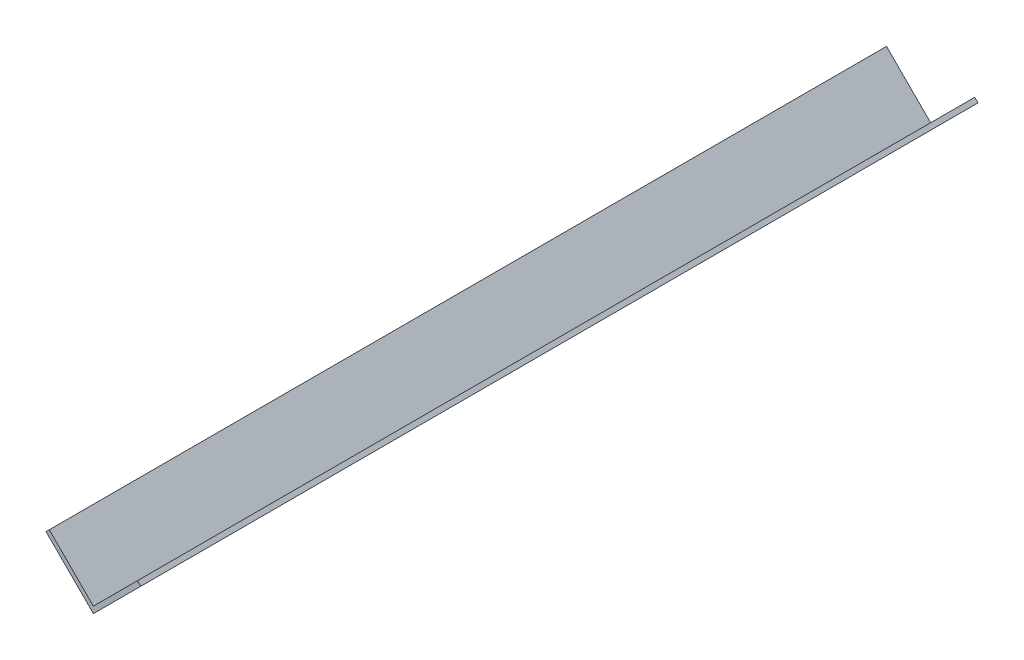
SolidWorks part; units mm, degrees
material "6061 Alloy"
ref_plane "Front Plane" through (0, 0, 0) normal (0, 0, 1) x (1, 0, 0)
ref_plane "Top Plane" through (0, 0, 0) normal (0, 1, 0) x (1, 0, 0)
ref_plane "Right Plane" through (0, 0, 0) normal (1, 0, 0) x (0, 0, -1)
sketch "Sketch1" plane through (0, 0, 0) normal (0, 0, 1) x (1, 0, 0)
  line L0 (0, 0) -> (-17.9605, 17.9605)
  line L1 (-17.9605, 17.9605) -> (-16.7257, 19.1953)
  line L2 (-16.7257, 19.1953) -> (0, 2.4696)
  line L3 (0, 2.4696) -> (16.7257, 19.1953)
  line L4 (16.7257, 19.1953) -> (17.9605, 17.9605)
  line L5 (17.9605, 17.9605) -> (0, 0)
  dimension "D1" = 1.7463
  dimension "D2" = 25.4
extrude "Boss-Extrude1" add sketch "Sketch1" along normal blind 317.5
